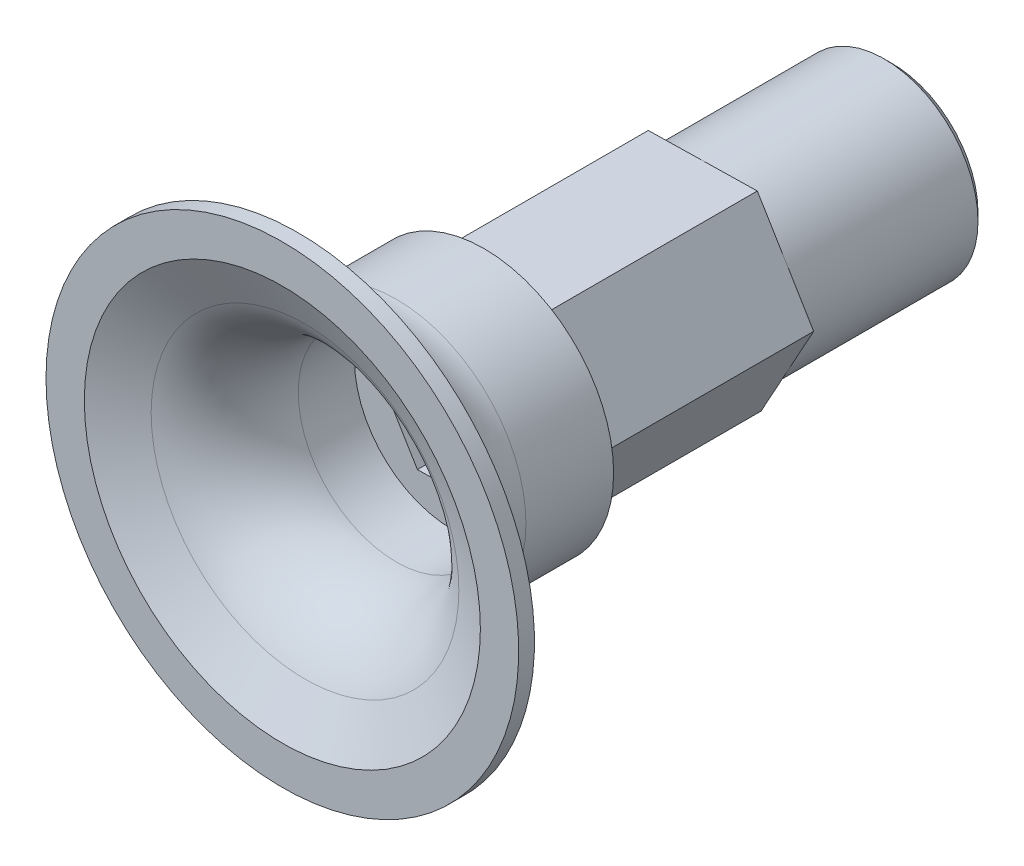
SolidWorks part; units mm, degrees
ref_plane "Front Plane" through (0, 0, 0) normal (0, 0, 1) x (1, 0, 0)
ref_plane "Top Plane" through (0, 0, 0) normal (0, 1, 0) x (1, 0, 0)
ref_plane "Right Plane" through (0, 0, 0) normal (1, 0, 0) x (0, 0, -1)
sketch "Sketch1" plane through (0, 0, 0) normal (0, 0, 1) x (1, 0, 0)
  circle A0 centre (0, 0) radius 5.95
  dimension "D1" = 11.9
extrude "Boss-Extrude1" add sketch "Sketch1" along normal blind 11.9
hole_wizard "M6 Tapped Hole1" positions "Sketch2" profile "Sketch3" tap size "M6" standard "DIN" end condition through all
sketch "Sketch2" plane through (0, 0, 0) normal (0, 0, -1) x (-1, 0, 0)
  point P0 (0, 0)
sketch "Sketch3" plane through (0, 0, 0) normal (1, 0, 0) x (0, 1, 0)
  line L0 (0, 0) -> (0, 11.9)
  line L1 (0, 11.9) -> (2.5, 11.9)
  line L2 (2.5, 11.9) -> (2.5, 0)
  line L5 (2.5, 0) -> (0, 0)
  line L11 (0, -6.35) -> (0, 107.95) construction
  dimension "Thru Tap Drill Dia." = 5
  dimension "Thru Tap Drill Depth" = 11.9
cosmetic thread "Hole Thread1" parameters "D2"=6
sketch "Sketch4" plane through (0, 0, 11.9) normal (0, 0, 1) x (1, 0, 0)
  line L1 (6.9213, 0.1346) -> (3.3441, 6.0614)
  line L2 (3.3441, 6.0614) -> (-3.5773, 5.9267)
  line L3 (-3.5773, 5.9267) -> (-6.9213, -0.1346)
  line L4 (-6.9213, -0.1346) -> (-3.3441, -6.0614)
  line L5 (-3.3441, -6.0614) -> (3.5773, -5.9267)
  line L6 (3.5773, -5.9267) -> (6.9213, 0.1346)
  circle A0 centre (0, 0) radius 5.9952 construction
extrude "Boss-Extrude2" add sketch "Sketch4" along normal blind 14
sketch "Sketch5" plane through (0, 0, 0) normal (0, 1, 0) x (1, 0, 0)
  line L0 (0, 0) -> (0, -32.8672) construction
  line L1 (-6.9213, -25.9) -> (-8.2242, -25.9)
  line L2 (-8.2242, -25.9) -> (-8.2242, -31.4662)
  line L3 (-10.6773, -35.4821) -> (-15, -37.7)
  line L4 (-15, -37.7) -> (-15, -38.7)
  line L5 (-15, -38.7) -> (0, -38.7)
  line L6 (0, -38.7) -> (0, -25.9)
  line L8 (-6.9213, -25.9) -> (0, -25.9)
  line L9 (3.3441, -25.9) -> (-3.5773, -25.9) construction
  arc A0 (-8.2242, -31.4662) -> (-10.6773, -35.4821) centre (-12.7378, -31.4662) cw
  dimension "D1" = 30
  dimension "D2" = 12.8
  dimension "D3" = 1
revolve "Revolve1" add sketch "Sketch5" angle 360 about L0
chamfer "Chamfer1" distance 0.5 angle 45 1 edges at (5.95, 0, 0)
shell "Shell1" thickness 2 removed face at (-15, 0, 38.7)
sketch "Sketch6" plane through (0, 0, 11.9) normal (0, 0, -1) x (-1, 0, 0)
  circle A1 centre (0, 0) radius 2.5
  circle A2 centre (0, 0) radius 2.5
  dimension "D1" = 0
extrude "Cut-Extrude1" cut sketch "Sketch6" against normal through all
